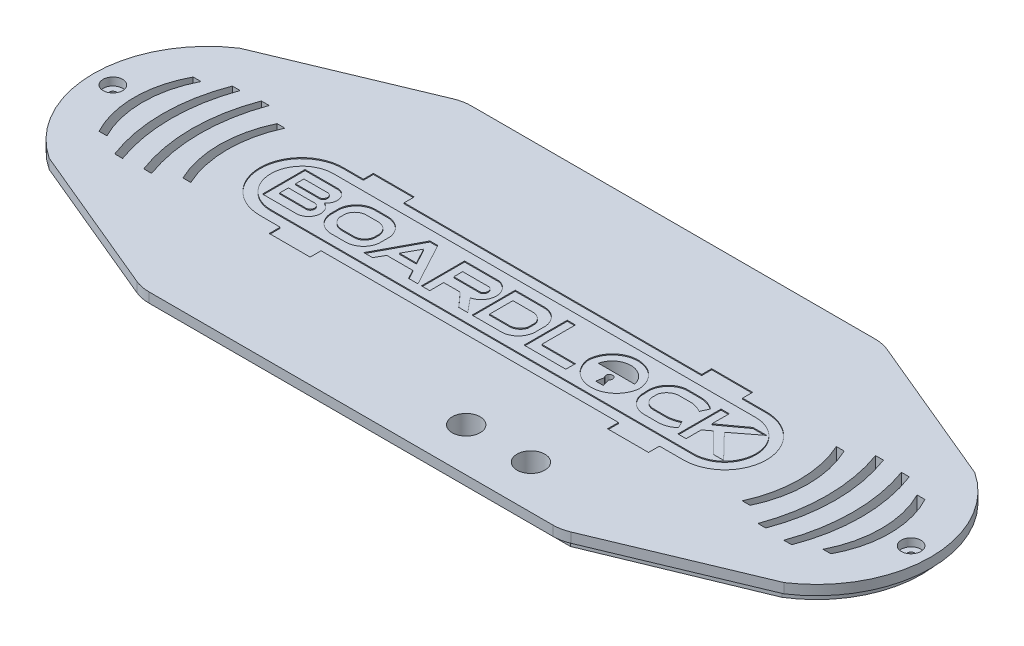
SolidWorks part; units mm, degrees
ref_plane "Front Plane" through (0, 0, 0) normal (0, 0, 1) x (1, 0, 0)
ref_plane "Top Plane" through (0, 0, 0) normal (0, 1, 0) x (1, 0, 0)
ref_plane "Right Plane" through (0, 0, 0) normal (1, 0, 0) x (0, 0, -1)
sketch "Sketch2" plane through (0, 0, 0) normal (0, 1, 0) x (1, 0, 0)
  line L0 (0, 0) -> (102, 0) construction
  line L1 (0, 0) -> (0, -77.2) construction
  line L2 (102, 0) -> (102, -77.2) construction
  line L3 (0, -77.2) -> (102, -77.2) construction
  line L4 (51, 0) -> (51, -77.2) construction
  line L5 (0, -38.6) -> (102, -38.6) construction
  line L6 (-2.5, 2.5) -> (104.5, 2.5)
  line L7 (-2.5, -79.7) -> (104.5, -79.7)
  line L8 (104.5, 2.5) -> (144.7372, -14.2911)
  line L9 (104.5, -79.7) -> (144.7372, -62.9089)
  line L10 (102, -38.6) -> (155.3, -38.6) construction
  line L11 (-2.5, -79.7) -> (-42.7372, -62.9089)
  line L12 (-2.5, 2.5) -> (-42.7372, -14.2911)
  line L13 (0, 0) -> (102, 0)
  line L14 (102, 0) -> (104.5, 0)
  line L15 (104.5, 0) -> (142.7026, -15.7437)
  line L16 (104.5, -77.2) -> (142.7026, -61.4563)
  line L17 (102, -77.2) -> (104.5, -77.2)
  line L18 (-2.5, -77.2) -> (-40.7026, -61.4563)
  line L19 (0, -77.2) -> (-2.5, -77.2)
  line L20 (-2.5, 0) -> (-40.7026, -15.7437)
  line L21 (0, 0) -> (-2.5, 0)
  line L22 (0, -77.2) -> (102, -77.2)
  line L23 (0.5, 0) -> (0.5, -77.2) construction
  line L24 (0, -76.7) -> (97.7329, -76.7) construction
  line L25 (0.5, -74.6) -> (97.3633, -74.6) construction
  line L26 (63.32, -77.2) -> (63.32, 0) construction
  line L27 (0.5, -62.6) -> (97.044, -62.6) construction
  line L28 (75.32, -62.6) -> (75.32, -74.6) construction
  line L29 (79.83, -62.6) -> (79.83, -74.6) construction
  line L30 (91.83, -62.6) -> (91.83, -74.6) construction
  line L31 (69.32, -62.6) -> (69.32, -74.6) construction
  line L32 (63.32, -68.6) -> (75.32, -68.6) construction
  line L33 (85.83, -62.6) -> (85.83, -74.6) construction
  line L34 (79.83, -68.6) -> (91.83, -68.6) construction
  arc A0 (144.7372, -14.2911) -> (144.7372, -62.9089) centre (128.65, -38.6) cw
  arc A1 (-42.7372, -14.2911) -> (-42.7372, -62.9089) centre (-26.65, -38.6) ccw
  arc A2 (142.7026, -15.7437) -> (142.7026, -61.4563) centre (128.65, -38.6) cw
  arc A3 (-40.7026, -15.7437) -> (-40.7026, -61.4563) centre (-26.65, -38.6) ccw
  circle A4 centre (69.32, -68.6) radius 3.55
  circle A5 centre (85.83, -68.6) radius 3.55
  point P16 (157.8, -38.6)
  dimension "D3" = 2.5
  dimension "D10" = 2.5
  dimension "D1" = 77.2
  dimension "D2" = 102
  dimension "D4" = 2.5
  dimension "D5" = 2.5
  dimension "D6" = 2.5
  dimension "D7" = 0.5
  dimension "D8" = 2.5
  dimension "D9" = 53.3
  dimension "D11" = 0.5
  dimension "D12" = 2.1
  dimension "D13" = 62.82
  dimension "D14" = 12
  dimension "D15" = 12
  dimension "D16" = 4.51
  dimension "D17" = 12
  dimension "D18" = 6
  dimension "D19" = 6
  dimension "D20" = 6
  dimension "D21" = 6
extrude "Boss-Extrude3" add sketch "Sketch2" along normal blind 2.5 contours L6 L8 A0 L9 L7 L11 A1 L12
extrude "Boss-Extrude4" add sketch "Sketch2<8>" against normal blind 2.5 contours L20 A3 L18 L19 L22 L17 L16 A2 L15 L14 L13 L21 region at (50.8464, 0, 38.4266)
sketch "Sketch2<8>" plane through (0, 0, 0) normal (0, 1, 0) x (1, 0, 0) same geometry as "Sketch2"
sketch "Sketch3" plane through (0, 2.5, 0) normal (0, 1, 0) x (1, 0, 0)
  line L0 (-55.8, -38.6) -> (157.8, -38.6) construction
  line L1 (51, 2.5) -> (51, -79.7) construction
  line L2 (-2.5, 2.5) -> (104.5, 2.5) construction
  line L3 (-2.5, -79.7) -> (104.5, -79.7) construction
  line L4 (201.4283, 144.6262) -> (1084.095, 144.6262) construction
  line L5 (-2.9873, -27.462) -> (1.9495, -27.462)
  line L6 (1.9495, -27.462) -> (1.9495, -24.9021)
  line L7 (1.9495, -24.9021) -> (12.3717, -24.9021)
  line L8 (12.3717, -24.9021) -> (12.3717, -27.462)
  line L9 (12.3717, -27.462) -> (88.2398, -27.462)
  line L10 (88.2398, -27.462) -> (88.2398, -24.9021)
  line L11 (88.2398, -24.9021) -> (98.6886, -24.9021)
  line L12 (98.6886, -24.9021) -> (98.6886, -27.462)
  line L13 (98.6886, -27.462) -> (104.6245, -27.462)
  line L14 (104.6245, -48.6746) -> (98.6886, -48.6746)
  line L15 (98.6886, -48.6746) -> (98.6886, -51.4646)
  line L16 (98.6886, -51.4646) -> (88.2398, -51.4646)
  line L17 (88.2398, -51.4646) -> (88.2398, -48.6746)
  line L18 (88.2398, -48.6746) -> (12.3717, -48.6746)
  line L19 (12.3717, -48.6746) -> (12.3717, -51.4646)
  line L20 (12.3717, -51.4646) -> (1.9495, -51.4646)
  line L21 (1.9495, -51.4646) -> (1.9495, -48.6746)
  line L22 (1.9495, -48.6746) -> (-2.9873, -48.6746)
  line L23 (-2.9873, -30.0692) -> (104.7002, -30.0692)
  line L24 (104.7002, -46.0158) -> (-3.1948, -46.0158)
  line L25 (-7.6306, -32.7625) -> (-7.6306, -43.6232)
  line L26 (-7.6306, -43.6232) -> (1.1441, -43.6232)
  line L27 (-7.6306, -32.7625) -> (0.7133, -32.7625)
  line L28 (5.3465, -39.2139) -> (5.3465, -36.9174)
  line L29 (-5.6807, -35.0072) -> (0.6, -35.0072)
  line L30 (-5.6807, -35.0072) -> (-5.6807, -37.1385)
  line L31 (-5.6807, -37.1385) -> (0.6, -37.1385)
  line L33 (-5.6807, -38.9524) -> (0.7133, -38.9524)
  line L34 (-5.6807, -38.9524) -> (-5.6807, -41.1744)
  line L35 (-5.6807, -41.1744) -> (0.7133, -41.1744)
  line L41 (10.1371, -35.0072) -> (13.3467, -35.0072)
  line L42 (9.866, -32.6184) -> (13.2281, -32.6184)
  line L43 (18.2229, -43.6232) -> (20.4629, -43.6232)
  line L44 (18.0967, -36.7888) -> (18.0967, -39.563)
  line L45 (16.1379, -37.4286) -> (16.1379, -38.7874)
  line L46 (13.8283, -43.6232) -> (10.2518, -43.6232)
  line L47 (20.4629, -43.6232) -> (21.7662, -41.3167)
  line L48 (13.6087, -41.3167) -> (10.2917, -41.3167)
  line L49 (21.7662, -41.3167) -> (28.4046, -41.3167)
  line L50 (7.3404, -38.9659) -> (7.3404, -37.4286)
  line L51 (28.4046, -41.3167) -> (29.6467, -43.6232)
  line L52 (29.6467, -43.6232) -> (32.0292, -43.6232)
  line L53 (32.0292, -43.6232) -> (26.1026, -32.6184)
  line L54 (26.1026, -32.6184) -> (24.0876, -32.6184)
  line L55 (24.0876, -32.6184) -> (18.2229, -43.6232)
  line L56 (22.9065, -39.2139) -> (27.2439, -39.2139)
  line L57 (27.2439, -39.2139) -> (25.0951, -35.224)
  line L58 (25.0951, -35.224) -> (22.9065, -39.2139)
  line L59 (32.928, -32.6184) -> (32.928, -43.6232)
  line L60 (32.928, -43.6232) -> (35.043, -43.6232)
  line L61 (35.043, -43.6232) -> (35.043, -40.0634)
  line L62 (35.043, -40.0634) -> (39.244, -40.0634)
  line L63 (39.244, -40.0634) -> (42.431, -43.6232)
  line L64 (42.431, -43.6232) -> (44.7378, -43.6232)
  line L65 (44.7378, -43.6232) -> (41.7936, -40.0634)
  line L66 (32.928, -32.6184) -> (41.7936, -32.6184)
  line L67 (35.043, -35.224) -> (35.043, -37.4805)
  line L68 (35.043, -37.4805) -> (41.7936, -37.4805)
  line L69 (35.043, -35.224) -> (41.7936, -35.224)
  line L70 (45.8463, -32.6184) -> (45.8463, -43.6232)
  line L71 (45.8463, -43.6232) -> (52.8329, -43.6232)
  line L72 (45.8463, -32.6184) -> (52.9687, -32.6184)
  line L73 (57.6458, -36.7888) -> (57.6458, -39.563)
  line L74 (47.8647, -35.224) -> (47.8647, -41.1744)
  line L75 (47.8647, -41.1744) -> (52.6, -41.1744)
  line L76 (47.8647, -35.224) -> (52.6, -35.224)
  line L77 (55.6246, -37.1385) -> (55.6246, -39.1866)
  line L78 (59.1096, -32.6184) -> (59.1096, -43.6232)
  line L79 (59.1096, -43.6232) -> (69.7525, -43.6232)
  line L80 (69.7525, -43.6232) -> (69.7525, -41.1876)
  line L81 (69.7525, -41.1876) -> (61.1954, -41.1876)
  line L82 (61.1954, -41.1876) -> (61.1954, -32.6184)
  line L83 (61.1954, -32.6184) -> (59.1096, -32.6184)
  line L84 (72.3273, -37.9056) -> (81.6057, -37.9056)
  line L85 (76.285, -40.2528) -> (75.9572, -42.1923)
  line L86 (75.9572, -42.1923) -> (77.8461, -42.1923)
  line L87 (77.8461, -42.1923) -> (77.3335, -40.2528)
  line L88 (90.3322, -35.0072) -> (93.3549, -35.0072)
  line L89 (96.0824, -35.9398) -> (96.9798, -33.9561)
  line L90 (92.9888, -32.6184) -> (89.5293, -32.6184)
  line L91 (86.9671, -37.333) -> (86.9671, -38.6)
  line L92 (86.9671, -38.6) -> (86.9671, -39.0585)
  line L93 (89.7665, -41.1876) -> (93.2664, -41.1876)
  line L94 (96.1597, -40.3804) -> (97.0399, -42.1923)
  line L95 (93.0498, -43.6232) -> (90.1278, -43.6232)
  line L96 (84.9417, -38.6) -> (84.9417, -39.5139)
  line L97 (98.3461, -32.6195) -> (98.3461, -43.6259)
  line L98 (98.3461, -43.6259) -> (100.4335, -43.6259)
  line L99 (100.4335, -43.6259) -> (100.4335, -39.7387)
  line L100 (100.4335, -39.7387) -> (102.2231, -38.4318)
  line L101 (102.2231, -38.4318) -> (107.3754, -43.6259)
  line L102 (107.3754, -43.6259) -> (110.0073, -43.6259)
  line L103 (110.0073, -43.6259) -> (103.904, -37.333)
  line L104 (103.904, -37.333) -> (110.0073, -32.6195)
  line L105 (110.0073, -32.6195) -> (106.4905, -32.6195)
  line L106 (106.4905, -32.6195) -> (100.4335, -37.0424)
  line L107 (100.4335, -37.0424) -> (100.4335, -32.6195)
  line L108 (100.4335, -32.6195) -> (98.3461, -32.6195)
  arc A0 (86.9671, -37.333) -> (90.3322, -35.0072) centre (90.1278, -38.3088) cw
  arc A1 (93.3549, -35.0072) -> (96.0824, -35.9398) centre (92.5616, -41.7819) cw
  arc A2 (-42.7372, -14.2911) -> (-42.7372, -62.9089) centre (-26.65, -38.6) ccw construction
  arc A3 (144.7372, -62.9089) -> (144.7372, -14.2911) centre (128.65, -38.6) ccw construction
  arc A4 (-2.9873, -27.462) -> (-2.9873, -48.6746) centre (-3.1948, -38.0683) ccw
  arc A5 (104.6245, -27.462) -> (104.6245, -48.6746) centre (104.776, -38.0683) cw
  arc A6 (-2.9873, -30.0692) -> (-3.1948, -46.0158) centre (-3.091, -38.0425) ccw
  arc A7 (104.7002, -30.0692) -> (104.7002, -46.0158) centre (104.7002, -38.0425) cw
  arc A8 (0.7133, -32.7625) -> (2.2325, -37.6827) centre (0.6, -35.492) cw
  arc A9 (1.1441, -43.6232) -> (2.2325, -37.6827) centre (1.0303, -40.5324) ccw
  arc A10 (0.6, -35.0072) -> (0.6, -37.1385) centre (0.3019, -36.0728) cw
  arc A11 (0.7133, -41.1744) -> (0.7133, -38.9524) centre (0.9838, -40.0634) ccw
  arc A12 (5.3465, -36.9174) -> (9.866, -32.6184) centre (10.1371, -37.4286) cw
  arc A13 (18.0967, -36.7888) -> (13.2281, -32.6184) centre (13.2836, -37.4805) ccw
  arc A14 (5.3465, -39.2139) -> (10.2518, -43.6232) centre (10.0037, -38.9659) ccw
  arc A15 (13.8283, -43.6232) -> (18.0967, -39.563) centre (13.6087, -39.1187) ccw
  arc A16 (10.1371, -35.0072) -> (7.3404, -37.4286) centre (10.2483, -37.9613) ccw
  arc A17 (13.3467, -35.0072) -> (16.1379, -37.4286) centre (13.2781, -37.9056) cw
  arc A18 (16.1379, -38.7874) -> (13.6087, -41.3167) centre (13.3904, -38.5692) cw
  arc A19 (10.2917, -41.3167) -> (7.3404, -38.9659) centre (10.2917, -38.2887) cw
  arc A20 (41.7936, -35.224) -> (41.7936, -37.4805) centre (41.488, -36.3523) cw
  arc A21 (41.7936, -40.0634) -> (41.7936, -32.6184) centre (40.9073, -36.3409) ccw
  arc A22 (52.9687, -32.6184) -> (57.6458, -36.7888) centre (53.222, -37.0421) cw
  arc A23 (57.6458, -39.563) -> (52.8329, -43.6232) centre (53.2093, -39.1866) cw
  arc A24 (52.6, -35.224) -> (55.6246, -37.1385) centre (52.8789, -38.1299) cw
  arc A25 (55.6246, -39.1866) -> (52.6, -41.1744) centre (52.8755, -38.2986) cw
  arc A26 (70.3877, -38.6) -> (83.4404, -38.6) centre (76.9141, -38.8997) cw
  arc A27 (70.3877, -38.6) -> (83.4404, -38.6) centre (76.9141, -37.8504) ccw
  arc A28 (76.285, -40.2528) -> (77.3335, -40.2528) centre (76.8092, -39.581) cw
  arc A29 (72.3273, -37.9056) -> (81.6057, -37.9056) centre (76.9665, -38.9919) cw
  arc A30 (96.9798, -33.9561) -> (92.9888, -32.6184) centre (93.0498, -39.0585) ccw
  arc A31 (89.5293, -32.6184) -> (84.9417, -38.6) centre (89.9999, -37.7293) ccw
  arc A32 (86.9671, -39.0585) -> (89.7665, -41.1876) centre (89.6538, -38.4308) ccw
  arc A33 (93.2664, -41.1876) -> (96.1597, -40.3804) centre (92.4973, -32.8415) ccw
  arc A34 (84.9417, -39.5139) -> (90.1278, -43.6232) centre (89.7907, -38.7214) ccw
  arc A35 (93.0498, -43.6232) -> (97.0399, -42.1923) centre (93.1901, -37.7354) ccw
extrude "Logo" cut sketch "Sketch3" against normal blind 0.25 contours L26 A9 A8 L27 L25 A11 L35 L34 L33 L29 A10 L31 L30 | L46 A15 L44 A13 L42 A12 L28 A14 L48 A19 L50 A16 L41 A17 L45 A18 | L54 L55 L43 L47 L49 L51 L52 L53 L58 L57 L56 | L65 A21 L66 L59 L60 L61 L62 L63 L64 L69 A20 L68 L67 | A23 L73 A22 L72 L70 L71 L77 A25 L75 L74 L76 A24 | A26 A27 L85 A28 L87 L86 L84 A29 | L95 A35 L94 A33 L93 A32 L92 L91 A0 L88 A1 L89 A30 L90 A31 L96 A34 | L107 L108 L97 L98 L99 L100 L101 L102 L103 L104 L105 L106 | L82 L83 L78 L79 L80 L81 | A4 L22 L21 L20 L19 L18 L17 L16 L15 L14 A5 L13 L12 L11 L10 L9 L8 L7 L6 L5 | A6 L24 A7 L23 | L78 L79 L80 L81 L82 L83 region at (-2.2321, 2.5, 38.3038) region at (5.5149, 2.5, 38.0657) region at (21.3111, 2.5, 38.2038) region at (37.3608, 2.5, 32.7798) region at (49.4075, 2.5, 32.7799) region at (60.1525, 2.5, 32.7715) region at (88.1536, 2.5, 35.4525) region at (102.8661, 2.5, 37.8921) region at (76.9141, 2.5, 32.5442)
fillet "Fillet1" radius 10 4 edges at (-2.5, 1.25, -2.5) (104.5, 1.25, -2.5) (104.5, 1.25, 79.7) (-2.5, 1.25, 79.7)
sketch "Sketch4" plane through (0, 2.5, 0) normal (0, 1, 0) x (1, 0, 0)
  line L0 (-55.8, -38.6) -> (157.8, -38.6) construction
  line L1 (51, 2.5) -> (51, -79.7) construction
  line L2 (-0.4972, 2.5) -> (102.4972, 2.5) construction
  line L3 (-0.4972, -79.7) -> (102.4972, -79.7) construction
  line L4 (-42.3364, -26.6) -> (-42.3364, -50.6) construction
  line L5 (-40.3364, -26.6) -> (-40.3364, -50.6) construction
  line L6 (-35.3364, -23.6) -> (-35.3364, -53.6) construction
  line L7 (-33.3364, -23.6) -> (-33.3364, -53.6) construction
  line L8 (-28.3364, -23.2) -> (-28.3364, -53.2) construction
  line L9 (-26.3364, -23.2) -> (-26.3364, -53.2) construction
  line L10 (-21.3364, -26.2) -> (-21.3364, -50.2) construction
  line L11 (-19.3364, -26.2) -> (-19.3364, -50.2) construction
  line L12 (-42.3364, -26.6) -> (-40.3364, -26.6)
  line L13 (-42.3364, -50.6) -> (-40.3364, -50.6)
  line L14 (-35.3364, -53.6) -> (-33.3364, -53.6)
  line L15 (-35.3364, -23.6) -> (-33.3364, -23.6)
  line L16 (-28.3364, -23.2) -> (-26.3364, -23.2)
  line L17 (-28.3364, -53.2) -> (-26.3364, -53.2)
  line L18 (-21.3364, -50.2) -> (-19.3364, -50.2)
  line L19 (-21.3364, -26.2) -> (-19.3364, -26.2)
  line L20 (121.3364, -26.2) -> (121.3364, -50.2) construction
  line L21 (123.3364, -26.2) -> (123.3364, -50.2) construction
  line L22 (128.3364, -23.2) -> (128.3364, -53.2) construction
  line L23 (130.3364, -23.2) -> (130.3364, -53.2) construction
  line L24 (135.3364, -23.6) -> (135.3364, -53.6) construction
  line L25 (137.3364, -23.6) -> (137.3364, -53.6) construction
  line L26 (142.3364, -26.6) -> (142.3364, -50.6) construction
  line L27 (144.3364, -26.6) -> (144.3364, -50.6) construction
  line L28 (123.3364, -26.2) -> (121.3364, -26.2)
  line L29 (123.3364, -50.2) -> (121.3364, -50.2)
  line L30 (130.3364, -53.2) -> (128.3364, -53.2)
  line L31 (130.3364, -23.2) -> (128.3364, -23.2)
  line L32 (137.3364, -23.6) -> (135.3364, -23.6)
  line L33 (137.3364, -53.6) -> (135.3364, -53.6)
  line L34 (144.3364, -50.6) -> (142.3364, -50.6)
  line L35 (144.3364, -26.6) -> (142.3364, -26.6)
  arc A0 (-42.7372, -14.2911) -> (-42.7372, -62.9089) centre (-26.65, -38.6) ccw construction
  arc A1 (144.7372, -62.9089) -> (144.7372, -14.2911) centre (128.65, -38.6) ccw construction
  arc A2 (-42.3364, -26.6) -> (-42.3364, -50.6) centre (-19.91, -38.6) ccw
  arc A3 (-40.3364, -26.6) -> (-40.3364, -50.6) centre (-16.7181, -38.6) ccw
  arc A4 (-35.3364, -23.6) -> (-35.3364, -53.6) centre (3.8054, -38.6) ccw
  arc A5 (-33.3364, -53.6) -> (-33.3364, -23.6) centre (8.2465, -38.6) cw
  arc A6 (-28.3364, -23.2) -> (-28.3364, -53.2) centre (11.3609, -38.2) ccw
  arc A7 (-26.3364, -23.2) -> (-26.3364, -53.2) centre (14.8909, -38.2) ccw
  arc A8 (-21.3364, -26.2) -> (-21.3364, -50.2) centre (3.9499, -38.2) ccw
  arc A9 (-19.3364, -26.2) -> (-19.3364, -50.2) centre (6.9686, -38.2) ccw
  arc A10 (121.3364, -26.2) -> (121.3364, -50.2) centre (95.0314, -38.2) cw
  arc A11 (123.3364, -26.2) -> (123.3364, -50.2) centre (98.0501, -38.2) cw
  arc A12 (128.3364, -23.2) -> (128.3364, -53.2) centre (87.1091, -38.2) cw
  arc A13 (130.3364, -23.2) -> (130.3364, -53.2) centre (90.6391, -38.2) cw
  arc A14 (135.3364, -53.6) -> (135.3364, -23.6) centre (93.7535, -38.6) ccw
  arc A15 (137.3364, -23.6) -> (137.3364, -53.6) centre (98.1946, -38.6) cw
  arc A16 (142.3364, -26.6) -> (142.3364, -50.6) centre (118.7181, -38.6) cw
  arc A17 (144.3364, -26.6) -> (144.3364, -50.6) centre (121.91, -38.6) cw
  dimension "D1" = 24
  dimension "D2" = 12
  dimension "D3" = 30
  dimension "D4" = 15
  dimension "D5" = 2
  dimension "D6" = 2
  dimension "D7" = 2
  dimension "D8" = 2
  dimension "D9" = 7
  dimension "D10" = 7
  dimension "D11" = 7
extrude "SoundGaps" cut sketch "Sketch4" against normal up to next
sketch "Sketch5" plane through (0, 2.5, 0) normal (0, 1, 0) x (1, 0, 0)
  circle A2 centre (69.32, -68.6) radius 3.55
  circle A3 centre (85.83, -68.6) radius 3.55
  dimension "D1" = 7.1
extrude "Buttons" cut sketch "Sketch5" against normal up to next
extrude "Cut-Extrude5" cut sketch "Sketch3<5>" against normal up to next contours A29 L84 | L85 L86 L87 A28 region at (76.9665, 2.5, 36.3712)
sketch "Sketch3<5>" plane through (0, 2.5, 0) normal (0, 1, 0) x (1, 0, 0) same geometry as "Sketch3"
sketch "Sketch9" plane through (0, 2.5, 0) normal (0, 1, 0) x (1, 0, 0)
  line L0 (-55.8, -38.6) -> (157.8, -38.6) construction
  arc A0 (-42.7372, -14.2911) -> (-42.7372, -62.9089) centre (-26.65, -38.6) ccw construction
  arc A1 (144.7372, -62.9089) -> (144.7372, -14.2911) centre (128.65, -38.6) ccw construction
  circle A2 centre (-50.8, -38.6) radius 2.5
  circle A3 centre (-50.8, -38.6) radius 0.9
  circle A4 centre (152.8, -38.6) radius 2.5
  circle A5 centre (152.8, -38.6) radius 0.9
  dimension "D2" = 5
  dimension "D1" = 5
extrude "Cut-Extrude6" cut sketch "Sketch9" against normal blind 2 contours A4 | A2
extrude "Cut-Extrude7" cut sketch "Sketch9<4>" against normal up to next contours A5 | A3
sketch "Sketch9<4>" plane through (0, 2.5, 0) normal (0, 1, 0) x (1, 0, 0) same geometry as "Sketch9"
